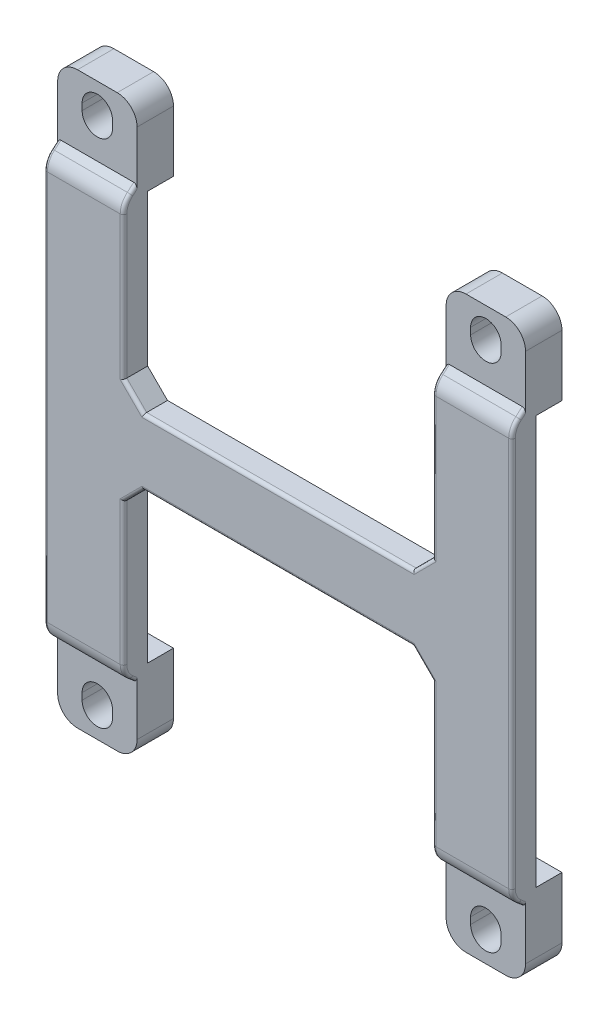
SolidWorks part; units mm, degrees
ref_plane "Front Plane" through (0, 0, 0) normal (0, 0, 1) x (1, 0, 0)
ref_plane "Top Plane" through (0, 0, 0) normal (0, 1, 0) x (1, 0, 0)
ref_plane "Right Plane" through (0, 0, 0) normal (1, 0, 0) x (0, 0, -1)
sketch "Sketch1" plane through (0, 0, 0) normal (0, 0, 1) x (1, 0, 0)
  line L0 (-44.8726, 37.3715) -> (-32.8726, 37.3715)
  line L1 (-44.8726, 37.3715) -> (-44.8726, 27.3715)
  line L2 (-44.8726, 27.3715) -> (-32.8726, 27.3715)
  line L3 (-32.8726, 37.3715) -> (-32.8726, 27.3715)
  line L4 (-44.8726, 37.3715) -> (-32.8726, 27.3715) construction
  line L5 (-44.8726, 27.3715) -> (-32.8726, 37.3715) construction
  line L6 (13.8274, 37.3715) -> (25.8274, 37.3715)
  line L7 (13.8274, 37.3715) -> (13.8274, 27.3715)
  line L8 (13.8274, 27.3715) -> (25.8274, 27.3715)
  line L9 (25.8274, 37.3715) -> (25.8274, 27.3715)
  line L10 (13.8274, 37.3715) -> (25.8274, 27.3715) construction
  line L11 (13.8274, 27.3715) -> (25.8274, 37.3715) construction
  line L12 (-44.8726, -38.7785) -> (-32.8726, -38.7785)
  line L13 (-44.8726, -38.7785) -> (-44.8726, -48.7785)
  line L14 (-44.8726, -48.7785) -> (-32.8726, -48.7785)
  line L15 (-32.8726, -38.7785) -> (-32.8726, -48.7785)
  line L16 (-44.8726, -38.7785) -> (-32.8726, -48.7785) construction
  line L17 (-44.8726, -48.7785) -> (-32.8726, -38.7785) construction
  line L18 (13.8274, -38.7785) -> (25.8274, -38.7785)
  line L19 (13.8274, -38.7785) -> (13.8274, -48.7785)
  line L20 (13.8274, -48.7785) -> (25.8274, -48.7785)
  line L21 (25.8274, -38.7785) -> (25.8274, -48.7785)
  line L22 (13.8274, -38.7785) -> (25.8274, -48.7785) construction
  line L23 (13.8274, -48.7785) -> (25.8274, -38.7785) construction
  line L24 (-44.8726, 27.3715) -> (-44.8726, -38.7785)
  line L25 (-32.8726, -38.7785) -> (-32.8726, 27.3715)
  line L26 (13.8274, 27.3715) -> (13.8274, -38.7785)
  line L27 (25.8274, 27.3715) -> (25.8274, -38.7785)
  line L28 (-32.8726, -5.7035) -> (13.8274, -5.7035) construction
  line L29 (-44.8726, -0.7035) -> (25.8274, -0.7035)
  line L30 (-44.8726, -0.7035) -> (-44.8726, -10.7035)
  line L31 (-44.8726, -10.7035) -> (25.8274, -10.7035)
  line L32 (25.8274, -0.7035) -> (25.8274, -10.7035)
  line L33 (-44.8726, -0.7035) -> (25.8274, -10.7035) construction
  line L34 (-44.8726, -10.7035) -> (25.8274, -0.7035) construction
  line L35 (-38.8726, 32.3715) -> (-38.8726, 33.3715) construction
  line L36 (-41.1726, 32.3715) -> (-41.1726, 33.3715)
  line L37 (-36.5726, 32.3715) -> (-36.5726, 33.3715)
  line L38 (-9.5226, -5.7035) -> (-9.5226, 17.21) construction
  line L39 (19.8274, 32.3715) -> (19.8274, 33.3715) construction
  line L40 (17.5274, 32.3715) -> (17.5274, 33.3715)
  line L41 (22.1274, 32.3715) -> (22.1274, 33.3715)
  line L42 (-38.8726, -43.7785) -> (-38.8726, -44.7785) construction
  line L43 (-36.5726, -43.7785) -> (-36.5726, -44.7785)
  line L44 (-41.1726, -43.7785) -> (-41.1726, -44.7785)
  line L45 (19.8274, -43.7785) -> (19.8274, -44.7785) construction
  line L46 (22.1274, -43.7785) -> (22.1274, -44.7785)
  line L47 (17.5274, -43.7785) -> (17.5274, -44.7785)
  circle A0 centre (-38.8726, 32.3715) radius 2.3
  circle A1 centre (19.8274, 32.3715) radius 2.3
  circle A2 centre (-38.8726, -43.7785) radius 2.3
  circle A3 centre (19.8274, -43.7785) radius 2.3
  circle A4 centre (-38.8726, 32.3715) radius 2.8702 construction
  circle A5 centre (19.8274, 32.3715) radius 2.8702 construction
  circle A6 centre (-38.8726, -43.7785) radius 2.8702 construction
  circle A7 centre (19.8274, -43.7785) radius 2.8702 construction
  arc A8 (-41.1726, 32.3715) -> (-36.5726, 32.3715) centre (-38.8726, 32.3715) ccw
  arc A9 (-36.5726, 33.3715) -> (-41.1726, 33.3715) centre (-38.8726, 33.3715) ccw
  arc A10 (17.5274, 32.3715) -> (22.1274, 32.3715) centre (19.8274, 32.3715) ccw
  arc A11 (22.1274, 33.3715) -> (17.5274, 33.3715) centre (19.8274, 33.3715) ccw
  arc A12 (-36.5726, -43.7785) -> (-41.1726, -43.7785) centre (-38.8726, -43.7785) ccw
  arc A13 (-41.1726, -44.7785) -> (-36.5726, -44.7785) centre (-38.8726, -44.7785) ccw
  arc A14 (22.1274, -43.7785) -> (17.5274, -43.7785) centre (19.8274, -43.7785) ccw
  arc A15 (17.5274, -44.7785) -> (22.1274, -44.7785) centre (19.8274, -44.7785) ccw
  point P26 (-9.5226, -5.7035)
  point P31 (-38.8726, 32.8715)
  point P48 (19.8274, 32.8715)
  point P54 (-38.8726, -44.2785)
  point P61 (19.8274, -44.2785)
  dimension "D1" = 4.6
  dimension "D2" = 12
  dimension "D3" = 10
  dimension "D4" = 10
  dimension "D5" = 1
extrude "Boss-Extrude1" add sketch "Sketch1" along normal blind 3 and the other way blind 4.55 contours L3 L0 L1 L2 A0 | L24 L29 L25 L2 | L24 L31 L25 L29 | L31 L24 L12 L25 | L15 L12 L13 L14 A2 | L31 L26 L18 L27 | L21 L18 L19 L20 A3 | L26 L31 L27 L29 | L25 L31 L26 L29 | L26 L29 L27 L8 | L9 L6 L7 L8 A1 region at (-38.8726, 37.2153, 0) region at (-38.8726, 13.334, 0) region at (-38.8726, -5.7035, 0) region at (-9.5226, -5.7035, 0) region at (-38.8726, -24.741, 0) region at (19.8274, -5.7035, 0) region at (19.8274, 13.334, 0) region at (-38.8726, -38.9347, 0) region at (19.8274, -24.741, 0) region at (13.9836, 32.3715, 0) region at (19.8274, -38.9347, 0)
sketch "Sketch5" plane through (0, 0, -4.55) normal (0, 0, -1) x (-1, 0, 0)
  line L0 (-25.8274, 37.3715) -> (-25.8274, -48.7785) construction
  line L1 (-25.8274, 25.1715) -> (-13.8274, 25.1715)
  line L2 (-25.8274, 25.1715) -> (-25.8274, -36.5695)
  line L3 (-25.8274, -36.5695) -> (-13.8274, -36.5695)
  line L4 (-13.8274, 25.1715) -> (-13.8274, -36.5695)
  line L5 (32.8726, 25.1715) -> (44.8726, 25.1715)
  line L6 (32.8726, 25.1715) -> (32.8726, -36.5695)
  line L7 (32.8726, -36.5695) -> (44.8726, -36.5695)
  line L8 (44.8726, 25.1715) -> (44.8726, -36.5695)
  line L9 (-25.8274, -0.7035) -> (44.8726, -0.7035)
  line L10 (-25.8274, -0.7035) -> (-25.8274, -10.7035)
  line L11 (-25.8274, -10.7035) -> (44.8726, -10.7035)
  line L12 (44.8726, -0.7035) -> (44.8726, -10.7035)
  line L13 (-31.8234, 25.1715) -> (50.8726, 25.1715) construction
  line L14 (32.8726, 37.3715) -> (32.8726, -0.7035) construction
  line L15 (-13.8274, -10.7035) -> (-13.8274, -48.7785) construction
  line L16 (-25.8274, 37.3715) -> (-25.8274, -48.7785) construction
  line L17 (-26.1321, -36.5695) -> (-31.8234, -36.5695) construction
  line L18 (44.8726, 37.3715) -> (44.8726, -48.7785) construction
  line L19 (50.8726, -36.5695) -> (45.1812, -36.5695) construction
  line M2 (32.8726, 37.3715) -> (32.8726, -0.7035)
  line M3 (32.8726, -0.7035) -> (-13.8274, -0.7035)
  line M4 (-13.8274, -0.7035) -> (-13.8274, 37.3715)
  line M6 (-25.8274, 37.3715) -> (-25.8274, -48.7785)
  line M8 (-13.8274, -48.7785) -> (-13.8274, -10.7035)
  line M9 (-13.8274, -10.7035) -> (32.8726, -10.7035)
  line M10 (32.8726, -10.7035) -> (32.8726, -48.7785)
  line M12 (44.8726, -48.7785) -> (44.8726, 37.3715)
extrude "Cut-Extrude1" cut sketch "Sketch5" against normal blind 3.9 contours L9 L1 M6 M4 | L2 L11 L4 L9 | L11 L3 M6 M8 | L6 L4 M3 M9 | L6 L11 L8 L9 | L11 L7 M10 M12 | L9 L8 L5 M2 region at (19.8274, 12.234, -4.55) region at (19.8274, -5.7035, -4.55) region at (-9.5226, -5.7035, -4.55) region at (19.8274, -23.6365, -4.55) region at (-38.8726, -5.7035, -4.55) region at (-38.8726, 12.234, -4.55) region at (-38.8726, -23.6365, -4.55)
sketch "Sketch6" plane through (-44.8726, 0, 0) normal (-1, 0, 0) x (0, 0, 1)
  line L0 (3, 25.1715) -> (0.95, 26.8916)
  line L1 (3, 37.3715) -> (3, -48.7785) construction
  line L2 (-0.65, -36.5785) -> (3, -36.5785) construction
  line L3 (-0.65, 25.1715) -> (3, 25.1715) construction
  line L4 (0.95, 25.1715) -> (0.95, 37.3715)
  line L5 (-0.65, 25.1715) -> (-4.55, 25.1715) construction
  line L6 (-4.55, 37.3715) -> (3, 37.3715) construction
  line L7 (-4.55, 37.3715) -> (-4.55, 25.1715) construction
  line L8 (0.95, 37.3715) -> (3, 37.3715)
  line L9 (3, 37.3715) -> (3, 25.1715)
  line L10 (3, -5.7035) -> (0, -5.7035) construction
  line L12 (3, -48.7785) -> (3, -36.5785)
  line L13 (0.95, -48.7785) -> (3, -48.7785)
  line L14 (0.95, -36.5785) -> (0.95, -48.7785)
  line L15 (3, -36.5785) -> (0.95, -38.2987)
  line M9 (-4.55, -48.7785) -> (3, -48.7785)
  line M10 (3, -48.7785) -> (3, 37.3715)
  line M11 (3, 37.3715) -> (-4.55, 37.3715)
  dimension "D1" = 5.5
  dimension "D2" = 50
extrude "Cut-Extrude2" cut sketch "Sketch6" against normal through all contours L4 L0 M10 M11 | L15 L14 M10 M9 region at (-44.8726, 31.6907, 2.0009) region at (-44.8726, -43.0977, 2.0009)
chamfer "Chamfer1" distance 3 angle 45 4 edges at (-32.8726, -10.7035, 1.175) (-32.8726, -0.7035, 1.175) (13.8274, -10.7035, 1.175) (13.8274, -0.7035, 1.175)
fillet "Fillet1" radius 3 8 edges at (25.8274, -48.7785, -1.8) (13.8274, -48.7785, -1.8) (-32.8726, -48.7785, -1.8) (-44.8726, -48.7785, -1.8) (25.8274, 37.3715, -1.8) (13.8274, 37.3715, -1.8) (-32.8726, 37.3715, -1.8) (-44.8726, 37.3715, -1.8)
fillet "Fillet2" radius 3 4 edges at (19.8274, -36.5785, 3) (-38.8726, -36.5785, 3) (19.8274, 25.1715, 3) (-38.8726, 25.1715, 3)
fillet "Fillet3" radius 0.5 27 edges at (-32.8726, -37.8882, 1.4392) (-32.8726, -36.4474, 2.7189) (-44.8726, 26.4812, 1.4392) (-44.8726, 25.0404, 2.7189) (-44.8726, -37.8882, 1.4392) (-44.8726, -36.4474, 2.7189) (-32.8726, 26.4812, 1.4392) (-32.8726, 25.0404, 2.7189) (13.8274, 26.4812, 1.4392) (13.8274, 25.0404, 2.7189) (25.8274, 26.4812, 1.4392) (25.8274, 25.0404, 2.7189) (25.8274, -37.8882, 1.4392) (25.8274, -36.4474, 2.7189) (13.8274, -37.8882, 1.4392) (13.8274, -36.4474, 2.7189) (12.3274, -12.2035, 3) (-9.5226, -10.7035, 3) (-31.3726, -12.2035, 3) (-32.8726, -24.4415, 3) (-44.8726, -5.7035, 3) (-31.3726, 0.7965, 3) (-9.5226, -0.7035, 3) (12.3274, 0.7965, 3) (13.8274, 13.0345, 3) (25.8274, -5.7035, 3) (13.8274, -24.4415, 3)
equation "\"D2@Boss-Extrude1\"=4.55"
